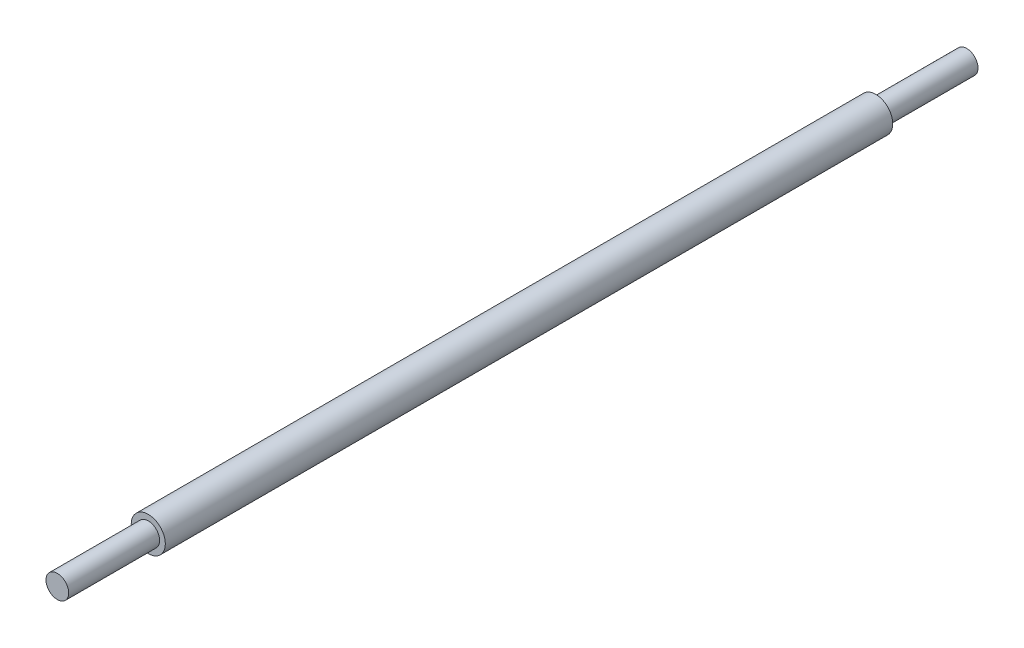
SolidWorks part; units mm, degrees
ref_plane "Front Plane" through (0, 0, 0) normal (0, 0, 1) x (1, 0, 0)
ref_plane "Top Plane" through (0, 0, 0) normal (0, 1, 0) x (1, 0, 0)
ref_plane "Right Plane" through (0, 0, 0) normal (1, 0, 0) x (0, 0, -1)
sketch "Sketch1" plane through (0, 0, 0) normal (0, 0, 1) x (1, 0, 0)
  circle A0 centre (0, 0) radius 2.3813
  dimension "D1" = 4.7625
extrude "Boss-Extrude1" add sketch "Sketch1" along normal blind 127
sketch "Sketch2" plane through (0, 0, 0) normal (0, 0, -1) x (-1, 0, 0)
  circle A0 centre (0, 0) radius 1.5875
  circle A1 centre (0, 0) radius 2.3813
  dimension "D1" = 3.175
extrude "Cut-Extrude1" cut sketch "Sketch2" against normal blind 12.7
sketch "Sketch3" plane through (0, 0, 127) normal (0, 0, 1) x (1, 0, 0)
  circle A0 centre (0, 0) radius 1.5875
  circle A1 centre (0, 0) radius 2.3813
  dimension "D1" = 3.175
extrude "Cut-Extrude2" cut sketch "Sketch3" against normal blind 12.7
